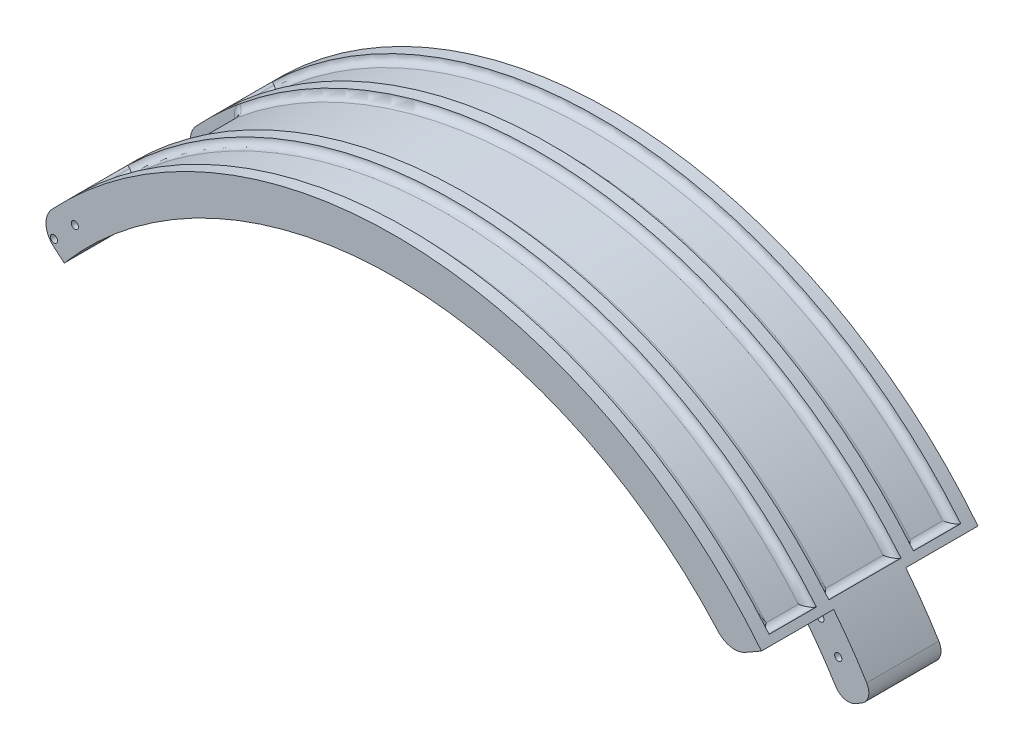
SolidWorks part; units mm, degrees
ref_plane "Front Plane" through (0, 0, 0) normal (0, 0, 1) x (1, 0, 0)
ref_plane "Top Plane" through (0, 0, 0) normal (0, 1, 0) x (1, 0, 0)
ref_plane "Right Plane" through (0, 0, 0) normal (1, 0, 0) x (0, 0, -1)
sketch "Sketch1" plane through (0, 0, 0) normal (0, 0, 1) x (1, 0, 0)
  line L0 (-45.7777, 38.7866) -> (-49.5926, 42.0188)
  line L3 (42.9614, 96.311) -> (43.6657, 96.311)
  line L5 (52.1044, 29.7512) -> (56.4464, 32.2305)
  arc A0 (52.1044, 29.7512) -> (-45.7777, 38.7866) centre (0, 0) ccw
  arc A1 (56.4464, 32.2305) -> (-49.5926, 42.0188) centre (0, 0) ccw
  dimension "D1" = 120
  dimension "D2" = 5
  dimension "D5" = 110
extrude "Boss-Extrude1" add sketch "Sketch1" along normal blind 30 contours L5 A1 L0 A0
ref_plane "Plane1" through (-49.5926, 42.0188, 0) normal (-0.763, 0.6464, 0) x (0, 0, -1)
sketch "Sketch2" plane through (-49.5926, 42.0188, 0) normal (-0.763, 0.6464, 0) x (0, 0, -1)
  line L0 (-30, 0) -> (0, 0) construction
  line L1 (-20, 0) -> (-10, 0)
  line L2 (-30, 0) -> (-30, -65) construction
  line L3 (-20, 0) -> (-10, 0)
  line L4 (-20, 0) -> (-20, -10)
  line L5 (-20, -10) -> (-10, -10)
  line L6 (-10, 0) -> (-10, -10)
  line L7 (0, -65) -> (0, 0) construction
  dimension "D1" = 10
  dimension "D2" = 10
  dimension "D3" = 10
  dimension "D4" = 10
extrude "Cut-Extrude1" cut sketch "Sketch2" against normal through all contours L6 L1 L4 L5
ref_plane "Plane2" through (56.4464, 32.2305, 0) normal (-0.8684, -0.4959, 0) x (0, 0, -1)
sketch "Sketch3" plane through (56.4464, 32.2305, 0) normal (-0.8684, -0.4959, 0) x (0, 0, -1)
  line L0 (-30, 0) -> (0, 0) construction
  line L1 (0, 0) -> (-10, 0)
  line L2 (0, 0) -> (0, -10)
  line L3 (0, -10) -> (-10, -10)
  line L4 (-10, 0) -> (-10, -10)
  line L5 (-30, 0) -> (-20, 0)
  line L6 (-30, 0) -> (-30, -10)
  line L7 (-30, -10) -> (-20, -10)
  line L8 (-20, 0) -> (-20, -10)
  line L9 (-30, 0) -> (-30, -65) construction
  dimension "D1" = 10
  dimension "D2" = 10
  dimension "D3" = 10
  dimension "D4" = 10
extrude "Cut-Extrude2" cut sketch "Sketch3" along normal blind 30
sketch "Sketch4" plane through (0, 0, 30) normal (0, 0, 1) x (1, 0, 0)
  line L0 (-47.6851, 40.4027) -> (-42.7122, 46.272) construction
  line L1 (-45.7777, 38.7866) -> (-49.5926, 42.0188) construction
  line L2 (-49.1044, 42.5882) -> (-45.2893, 39.3558)
  arc A0 (50.8159, 40.5308) -> (-49.5926, 42.0188) centre (0, 0) ccw construction
  arc A1 (46.4171, 38.0192) -> (-45.7777, 38.7866) centre (0, 0) ccw construction
  circle A2 centre (-47.1969, 40.972) radius 0.5
  dimension "D2" = 1
  dimension "D1" = 0.75
extrude "Cut-Extrude3" cut sketch "Sketch4" against normal through all both and the other way through all contours L0 A2 L2 | A2 L0 L2 | L0 L2 A2 | L2 L0 A2
sketch "Sketch5" plane through (0, 0, 20) normal (0, 0, 1) x (1, 0, 0)
  line L0 (48.6165, 39.275) -> (50.5171, 35.9464) construction
  line L1 (46.4171, 38.0192) -> (50.8159, 40.5308) construction
  line L2 (46.8948, 37.4283) -> (51.2853, 39.9352)
  line L3 (48.8615, 38.5512) -> (48.9884, 38.6237)
  arc A0 (52.1044, 29.7512) -> (46.4171, 38.0192) centre (0, 0) ccw construction
  arc A1 (56.4464, 32.2305) -> (50.8159, 40.5308) centre (0, 0) ccw construction
  circle A2 centre (48.9884, 38.6237) radius 0.5
  dimension "D2" = 1
  dimension "D1" = 0.75
extrude "Cut-Extrude5" cut sketch "Sketch5" against normal blind 30 contours L2 L0 A2 | L0 L2 A2 | A2 L0 L2 | L0 A2 L2
fillet "Fillet3" radius 3 2 edges at (46.4171, 38.0192, 5) (46.4171, 38.0192, 25)
fillet "Fillet5" radius 3 2 edges at (-49.5926, 42.0188, 25) (-49.5926, 42.0188, 5)
fillet "Fillet6" radius 2 4 edges at (52.1044, 29.7512, 15) (56.4464, 32.2305, 15) (-38.673, 45.8737, 15) (-42.5377, 49.1482, 15)
sketch "Sketch6" plane through (0, 0, 10) normal (0, 0, -1) x (-1, 0, 0)
  line L0 (-53.8132, 30.7269) -> (-54.682, 31.223) construction
  circle A0 centre (0, 0) radius 62.3023
  circle A3 centre (-51.4499, 35.1352) radius 0.5
  dimension "D1" = 1
  dimension "D2" = 5
extrude "Cut-Extrude6" cut sketch "Sketch6" against normal through all contours A0 A3 | A0 A3
sketch "Sketch7" plane through (0, 0, 0) normal (0, 0, -1) x (-1, 0, 0)
  circle A0 centre (0, 0) radius 62.5
  arc A1 (45.7777, 38.7866) -> (-44.8439, 39.8626) centre (0, 0) ccw construction
  circle A2 centre (44.31, 44.0781) radius 0.5
  dimension "D1" = 2.5
  dimension "D2" = 1
  dimension "D3" = 5
extrude "Cut-Extrude7" cut sketch "Sketch7" against normal through all both and the other way through all contours A0 A2 | A0 A2
scale "Scale1" scale about centroid uniform scaling yes scale factor 1.9329
scale "Scale2" scale about centroid uniform scaling yes scale factor 1.5
sketch "Sketch8" plane through (0, 0, -28.4902) normal (0, 0, -1) x (-1, 0, 0)
  line L0 (-135.7912, 14.6011) -> (-138.4354, 16.1109)
  line L1 (-133.8491, 10.0376) -> (-140.3502, 13.7496) construction
  line L2 (139.6254, 25.8534) -> (142.8228, 26.8651)
  line L4 (140.0386, 12.9042) -> (142.0327, 14.5937)
  line L5 (-135.7912, 14.6011) -> (-132.3616, 12.6428)
  arc A0 (144.7057, 24.8785) -> (-140.3502, 13.7496) centre (6.9828, -103.7634) ccw construction
  arc A1 (142.8228, 26.8651) -> (-138.4354, 16.1109) centre (6.9828, -103.7634) ccw
  arc A8 (142.0327, 14.5937) -> (142.5133, 22.8306) centre (138.3492, 18.9411) ccw
  arc A9 (142.5133, 22.8306) -> (-135.7912, 14.6011) centre (6.9828, -103.7634) ccw
  arc A10 (-132.3616, 12.6428) -> (-125.2774, 13.8054) centre (-129.5362, 17.591) ccw
  arc A11 (140.0386, 12.9042) -> (-125.2774, 13.8054) centre (6.9828, -103.7634) ccw
  arc A13 (139.6254, 25.8534) -> (-135.7912, 14.6011) centre (6.9828, -103.7634) ccw
  dimension "D1" = 3
extrude "Cut-Extrude8" cut sketch "Sketch8" against normal up to vertex (57.987 mm away) from vertex at -28.9935 starting at point (140.3502, 13.7497, 0.5032)
sketch "Sketch9" plane through (0, 0, -28.4902) normal (0, 0, -1) x (-1, 0, 0)
  line L0 (-138.4354, 16.1109) -> (-135.7912, 14.6011) construction
  line L1 (-138.4354, 16.1109) -> (-135.7912, 14.6011)
  line L3 (135.3744, 30.0655) -> (138.2785, 31.4318)
  arc A0 (127.0004, 37.6238) -> (-135.7912, 14.6011) centre (6.9828, -103.7634) ccw construction
  arc A1 (144.7057, 24.8785) -> (-140.3502, 13.7496) centre (6.9828, -103.7634) ccw construction
  arc A2 (127.0004, 37.6238) -> (-135.7912, 14.6011) centre (6.9828, -103.7634) ccw
  arc A3 (138.2785, 31.4318) -> (-138.4354, 16.1109) centre (6.9828, -103.7634) ccw
  arc A4 (135.3744, 30.0655) -> (-135.7912, 14.6011) centre (6.9828, -103.7634) ccw
extrude "Cut-Extrude9" cut sketch "Sketch9" against normal blind 19 from offset 5 contours A4 L3 A3 L1 offset against normal yes
sketch "Sketch10" plane through (0, 0, 58.4903) normal (0, 0, 1) x (1, 0, 0)
  line L0 (-135.3744, 30.0655) -> (-138.2785, 31.4318) construction
  line L1 (138.4354, 16.1109) -> (135.7912, 14.6011) construction
  line L2 (-143.972, 12.3049) -> (-139.7085, 8.6924)
  line L3 (133.8491, 10.0376) -> (140.3502, 13.7496)
  line L6 (-135.3744, 30.0655) -> (-138.2785, 31.4318)
  line L7 (138.4354, 16.1109) -> (135.7912, 14.6011)
  arc A0 (135.7912, 14.6011) -> (-135.3744, 30.0655) centre (-6.9828, -103.7634) ccw construction
  arc A1 (135.7912, 14.6011) -> (-135.3744, 30.0655) centre (-6.9828, -103.7634) ccw
  arc A4 (140.3502, 13.7496) -> (-144.7057, 24.8785) centre (-6.9828, -103.7634) ccw
  arc A5 (-144.7057, 24.8785) -> (-143.972, 12.3049) centre (-138.3492, 18.9411) ccw
  arc A6 (123.0353, 11.8122) -> (-139.7085, 8.6924) centre (-6.9828, -103.7634) ccw
  arc A7 (123.0353, 11.8122) -> (133.8491, 10.0376) centre (129.5362, 17.591) ccw
  arc A8 (138.4354, 16.1109) -> (-138.2785, 31.4318) centre (-6.9828, -103.7634) ccw
  dimension "D1" = 0
extrude "Cut-Extrude10" cut sketch "Sketch10" against normal blind 19 from offset 5 offset against normal yes
fillet "Fillet7" radius 3 18 edges at (-119.1345, 30.9907, 0.5033) (-119.1345, 30.9907, 29.4968) (-123.9236, 33.3195, 0.5033) (-123.9236, 33.3195, 29.4968) (-126.3136, 35.7814, 0.5033) (-126.3136, 35.7814, 29.4968) (135.7912, 14.6011, -13.9902) (3.5766, 81.3935, -4.4902) (-135.3744, 30.0655, -13.9902) (3.5766, 81.3935, -23.4902) (9.2029, 80.9867, 29.4968) (9.2029, 80.9867, 0.5033) (135.7912, 14.6011, 15) (-127.0004, 37.6238, 15) (-135.3744, 30.0655, 43.9903) (3.5766, 81.3935, 34.4903) (135.7912, 14.6011, 43.9903) (3.5766, 81.3935, 53.4903)
